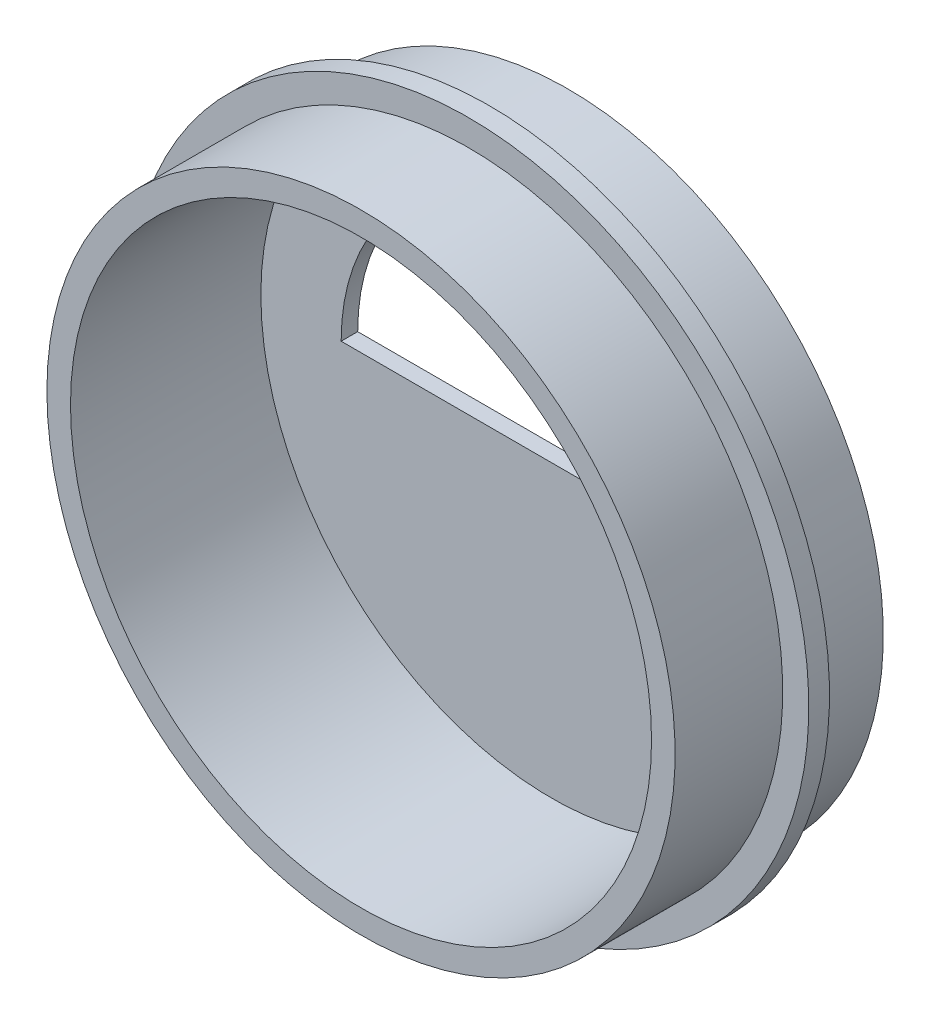
SolidWorks part; units mm, degrees
ref_plane "Front Plane" through (0, 0, 0) normal (0, 0, 1) x (1, 0, 0)
ref_plane "Top Plane" through (0, 0, 0) normal (0, 1, 0) x (1, 0, 0)
ref_plane "Right Plane" through (0, 0, 0) normal (1, 0, 0) x (0, 0, -1)
sketch "Sketch6" plane through (0, 0, 0) normal (1, 0, 0) x (0, 0, -1)
  line L0 (0, 0) -> (-40.103, 0) construction
  line L1 (0, 0) -> (0, 25.4) construction
  line L2 (0, 25.4) -> (-2, 25.4)
  line L3 (-2, 25.4) -> (-2, 35.1)
  line L4 (-2, 35.1) -> (-25, 35.1)
  line L5 (-25, 35.1) -> (-25, 37.95)
  line L6 (-25, 37.95) -> (-12, 37.95)
  line L7 (-12, 37.95) -> (-12, 41.1)
  line L8 (-12, 41.1) -> (-9.5, 41.1)
  line L9 (-9.5, 41.1) -> (-9.5, 38.1)
  line L10 (-9.5, 38.1) -> (0, 38.1)
  line L11 (0, 38.1) -> (0, 25.4)
  point P8 (0, 0)
  dimension "D1" = 9.7
  dimension "D2" = 25.4
  dimension "D3" = 25
  dimension "D4" = 23
  dimension "D5" = 2.85
  dimension "D6" = 3.15
  dimension "D7" = 2.5
  dimension "D8" = 13
  dimension "D9" = 38.1
revolve "Revolve1" add sketch "Sketch6" angle 360 about L0
sketch "Sketch7" plane through (0, 0, 0) normal (0, 0, -1) x (-1, 0, 0)
  line L0 (-25.4, 0) -> (25.4, 0)
  circle A0 centre (0, 0) radius 25.4 construction
  arc A1 (-25.4, 0) -> (25.4, 0) centre (0, 0) ccw
extrude "Boss-Extrude1" add sketch "Sketch7" against normal blind 2
